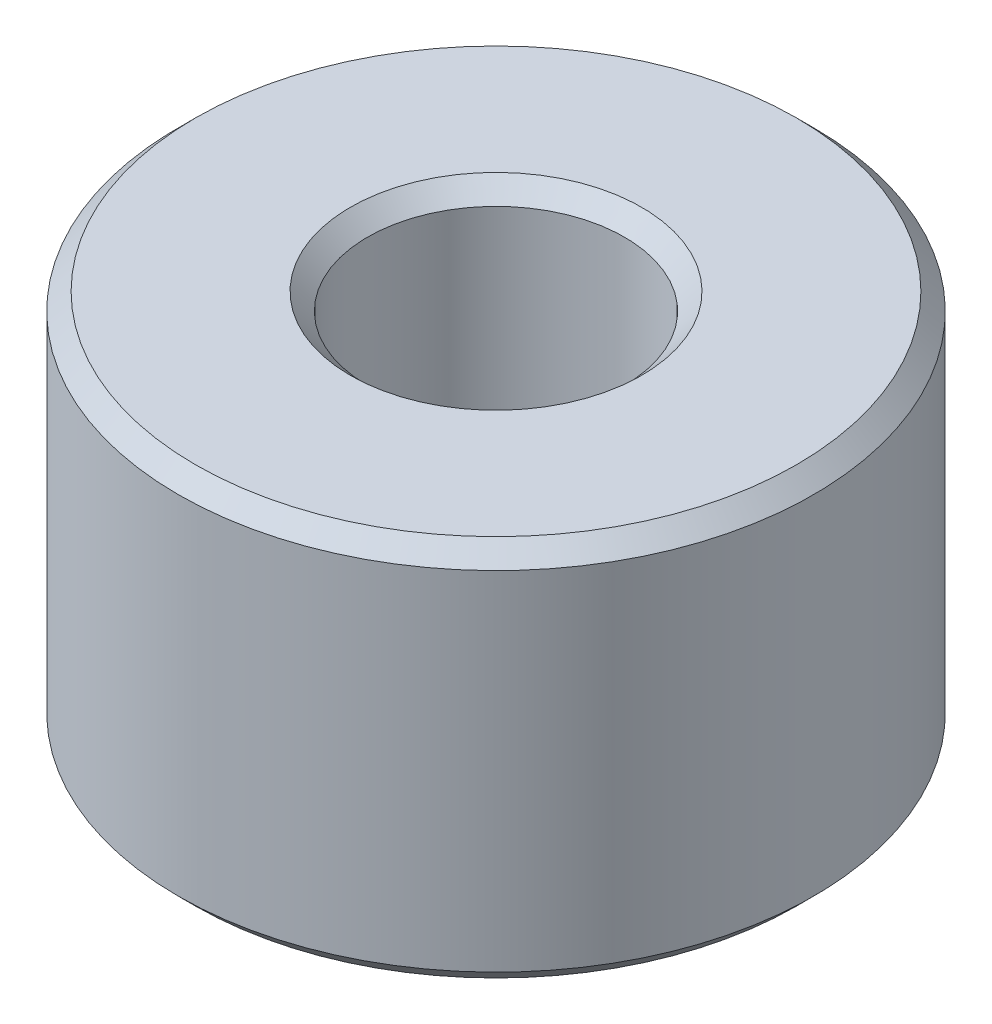
SolidWorks part; units mm, degrees
ref_plane "Front Plane" through (0, 0, 0) normal (0, 0, 1) x (1, 0, 0)
ref_plane "Top Plane" through (0, 0, 0) normal (0, 1, 0) x (1, 0, 0)
ref_plane "Right Plane" through (0, 0, 0) normal (1, 0, 0) x (0, 0, -1)
sketch "Sketch1" plane through (0, 0, 0) normal (0, 1, 0) x (1, 0, 0)
  circle A0 centre (0, 0) radius 55
  dimension "SLEEVE_OD" = 110
extrude "Boss-Extrude1" add sketch "Sketch1" along normal blind 66.1699
sketch "Sketch2" plane through (0, 0, 0) normal (0, 1, 0) x (1, 0, 0)
  circle A0 centre (0, 0) radius 22.2382
  dimension "BORE_D" = 44.4764
extrude "Cut-Extrude1" cut sketch "Sketch2" along normal through all
chamfer "Chamfer1" distance 2.9812 angle 45 4 edges at (0, 66.1699, 22.2382) (0, 0, 22.2382) (0, 0, 55) (0, 66.1699, 55)
